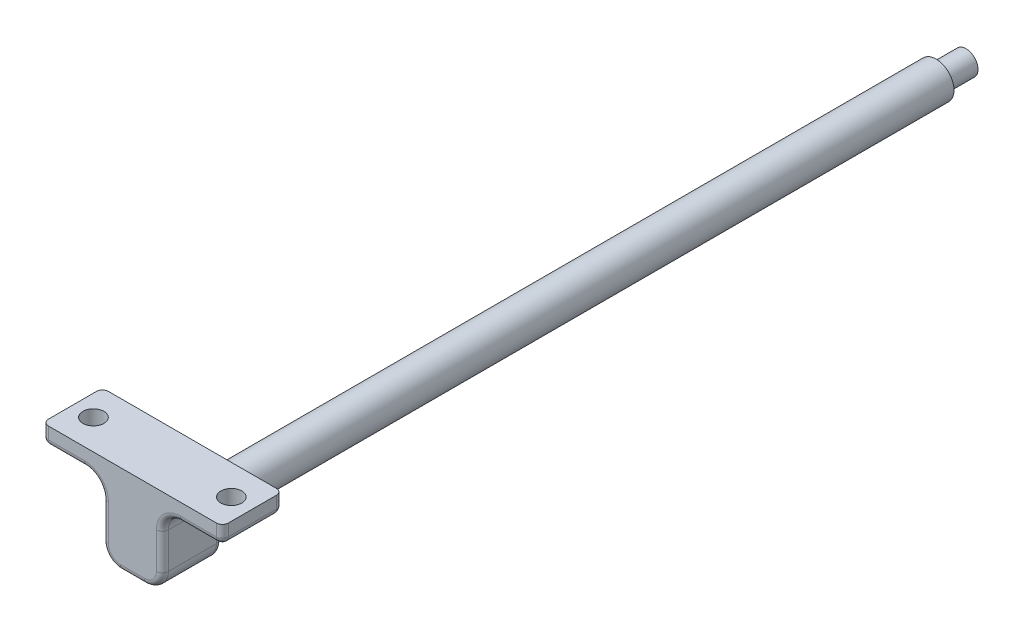
SolidWorks part; units mm, degrees
ref_plane "正面" through (0, 0, 0) normal (0, 0, 1) x (1, 0, 0)
ref_plane "平面" through (0, 0, 0) normal (0, 1, 0) x (1, 0, 0)
ref_plane "右側面" through (0, 0, 0) normal (1, 0, 0) x (0, 0, -1)
sketch "ｽｹｯﾁ1" plane through (0, 0, 0) normal (0, 0, 1) x (1, 0, 0)
  circle A0 centre (0, 0) radius 3
extrude "ﾎﾞｽ - 押し出し1" add sketch "ｽｹｯﾁ1" along normal blind 124
sketch "ｽｹｯﾁ2" plane through (0, 0, 0) normal (0, 0, -1) x (-1, 0, 0)
  circle A0 centre (0, 0) radius 2
extrude "ﾎﾞｽ - 押し出し2" add sketch "ｽｹｯﾁ2" along normal blind 5
sketch "ｽｹｯﾁ4" plane through (0, 0, 124) normal (0, 0, 1) x (1, 0, 0)
  line L0 (0, 10) -> (0, -5)
  line L1 (5, -5) -> (-5, -5)
  line L2 (5, -5) -> (5, 10)
  line L3 (5, 10) -> (-5, 10)
  line L4 (-5, -5) -> (-5, 10)
  line L5 (5, 10) -> (15, 10)
  line L6 (5, 10) -> (5, 7)
  line L7 (5, 7) -> (15, 7)
  line L8 (15, 10) -> (15, 7)
  line L9 (-15, 10) -> (-15, 7)
  line L10 (-5, 7) -> (-15, 7)
  line L11 (-5, 10) -> (-5, 7)
  line L12 (-5, 10) -> (-15, 10)
  line L13 (5, -5) -> (5, 10)
  line L14 (-5, -5) -> (-5, 10)
  circle A0 centre (0, 0) radius 3 construction
  circle M5 centre (0, 0) radius 3
  dimension "D3" = 5
  dimension "D4" = 5
  dimension "D1" = 15
  dimension "D2" = 10
  dimension "D5" = 3
  dimension "D6" = 10
extrude "ﾎﾞｽ - 押し出し4" add sketch "ｽｹｯﾁ4" along normal blind 10 separate body contours L8 L5 L2 L7 | L2 L3 L0 L1 M5 | L4 L1 L0 L3 M5 | L4 L12 L9 L10 | L0 M5 | L0 M5 region at (2.785, 3.0807, 124) region at (-2.785, 3.0807, 124) region at (1.2732, 0, 124) region at (-1.2732, 0, 124) region at (10, 8.5, 124) region at (-10, 8.5, 124)
fillet "ﾌｨﾚｯﾄ6" radius 3 4 edges at (5, 7, 129) (-5, 7, 129) (5, -5, 129) (-5, -5, 129)
fillet "ﾌｨﾚｯﾄ7" radius 1 20 edges at (5.8787, 6.1213, 134) (5, 1, 134) (4.1213, -4.1213, 134) (0, -5, 134) (-4.1213, -4.1213, 134) (-5, 1, 134) (-5.8787, 6.1213, 134) (5.8787, 6.1213, 124) (5, 1, 124) (4.1213, -4.1213, 124) (0, -5, 124) (-4.1213, -4.1213, 124) (-5, 1, 124) (-5.8787, 6.1213, 124) (15, 7, 129) (11.5, 7, 124) (11.5, 7, 134) (-15, 7, 129) (-11.5, 7, 134) (-11.5, 7, 124)
sketch "ｽｹｯﾁ5" plane through (0, 7, 0) normal (0, -1, 0) x (-1, 0, 0)
  line L0 (-15, -134) -> (-15, -124) construction
  line L1 (-8, -134) -> (-15, -134) construction
  line L2 (15, -134) -> (8, -134) construction
  line L3 (15, -124) -> (15, -134) construction
  circle A0 centre (-11.5, -129) radius 1.75
  circle A1 centre (11.5, -129) radius 1.75
  dimension "D1" = 3.5
  dimension "D6" = 3.5
  dimension "D2" = 3.5
  dimension "D3" = 5
  dimension "D4" = 5
  dimension "D5" = 3.5
extrude "ｶｯﾄ - 押し出し1" cut sketch "ｽｹｯﾁ5" against normal through all
fillet "ﾌｨﾚｯﾄ8" radius 1 8 edges at (-14.7071, 7.2929, 124.2929) (-14.7071, 7.2929, 133.7071) (14.7071, 7.2929, 124.2929) (14.7071, 7.2929, 133.7071) (-15, 9, 124) (-15, 9, 134) (15, 9, 124) (15, 9, 134)
